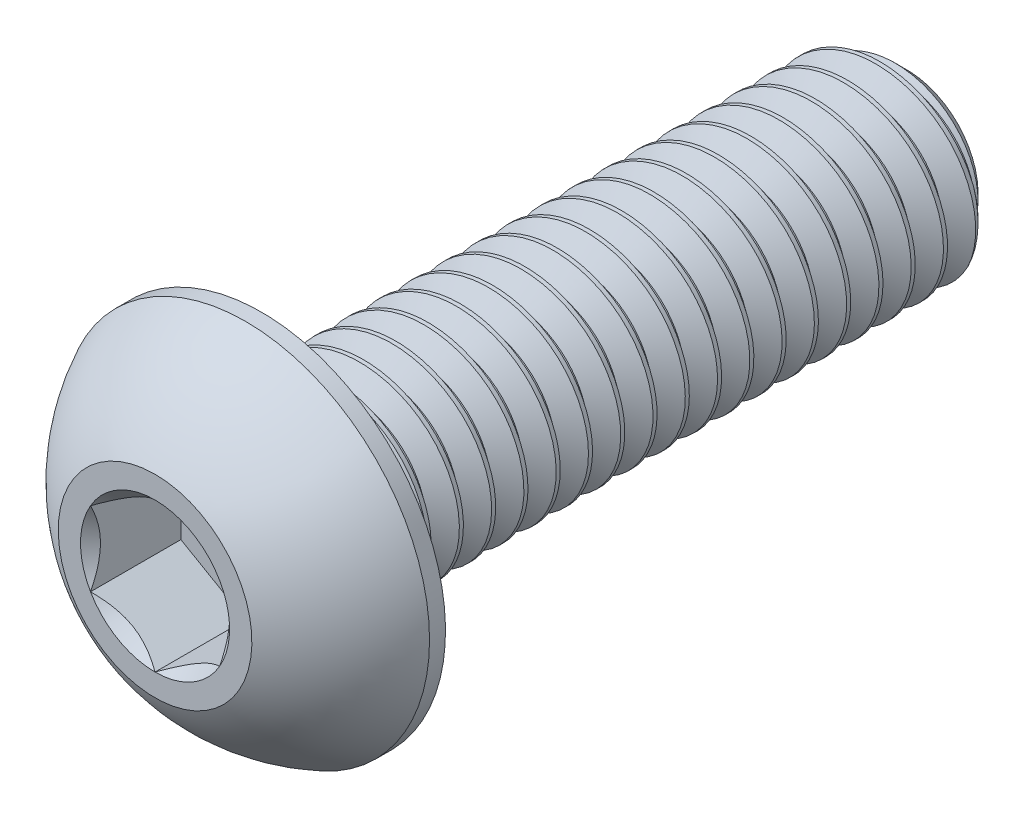
SolidWorks part; units mm, degrees
ref_plane "Front Plane" through (0, 0, 0) normal (0, 0, 1) x (1, 0, 0)
ref_plane "Top Plane" through (0, 0, 0) normal (0, 1, 0) x (1, 0, 0)
ref_plane "Right Plane" through (0, 0, 0) normal (1, 0, 0) x (0, 0, -1)
sketch "Sketch1" plane through (0, 0, 0) normal (1, 0, 0) x (0, 0, -1)
  line L0 (-5.825, 0) -> (5.825, 0) construction
  line L1 (-4.175, 2.85) -> (-4.175, -2.85) construction
  line L2 (5.825, 1.5) -> (5.825, -1.5) construction
  line L3 (5.7938, 1.5541) -> (6.0438, 1.1211) construction
  line L4 (6.0438, 1.1211) -> (6.2938, 1.5541) construction
  line L5 (6.2938, 1.5541) -> (5.7938, 1.5541) construction
  line L6 (5.825, 1.5) -> (6.2625, 1.5) construction
  line L7 (6.0438, 1.5541) -> (6.0438, 1.5) construction
  line L8 (6.0438, 1.5) -> (6.0438, 1.1752) construction
  line L9 (6.0438, 1.1752) -> (6.0438, 1.1211) construction
  line L10 (6.0125, 1.1752) -> (6.075, 1.1752)
  line L11 (5.8094, 1.5271) -> (6.2781, 1.5271)
  line L12 (6.075, 1.1752) -> (6.2781, 1.5271)
  line L13 (6.0125, 1.1752) -> (5.8094, 1.5271)
  line L14 (-5.825, 1) -> (-5.825, -1) construction
  line L15 (5.825, 1.5) -> (-4.175, 1.5) construction
  point P3 (-4.175, 0)
  point P6 (-4.425, 0)
  point P21 (6.0438, 1.5271)
  point P24 (-4.4225, 2.85)
  point P25 (4.575, -1.5)
  point P26 (-5.825, 1.5)
  dimension "Head Height" = 1.65
  dimension "Length" = 10
  dimension "Head Dia" = 5.7
  dimension "Thread Dia" = 3
  dimension "Pitch" = 0.5
  dimension "Drive Size" = 2
  dimension "D1" = 1.4
  dimension "D3" = 0.2475
  dimension "D4" = 1.25
sketch "Sketch2" plane through (0, 0, 0) normal (1, 0, 0) x (0, 0, -1)
  line L0 (-5.825, 0) -> (5.825, 0)
  line L1 (5.825, 0) -> (5.825, 1.1)
  line L2 (5.825, 1.5) -> (5.825, -1.5) construction
  line L3 (5.825, 1.1) -> (5.425, 1.5)
  line L4 (5.425, 1.5) -> (-4.175, 1.5)
  line L5 (-4.175, 2.85) -> (-4.175, -2.85) construction
  line L6 (-4.175, 1.5) -> (-4.175, 2.85)
  line L7 (-4.175, 2.85) -> (-4.4225, 2.85)
  line L8 (5.825, 1.5) -> (6.2625, 1.5) construction
  line L9 (-5.825, 0) -> (-5.825, 1.5)
  arc A0 (-5.825, 1.5) -> (-4.4225, 2.85) centre (-3.0302, 0) cw
  dimension "D1" = 0.4
  dimension "D2" = 45
revolve "Revolve1" add sketch "Sketch2" angle 360 about L0
sketch "Sketch3" plane through (0, 0, 5.825) normal (0, 0, 1) x (1, 0, 0)
  line L1 (0, 1.1547) -> (-1, 0.5774)
  line L2 (-1, 0.5774) -> (-1, -0.5774)
  line L3 (-1, -0.5774) -> (0, -1.1547)
  line L4 (0, -1.1547) -> (1, -0.5774)
  line L5 (1, -0.5774) -> (1, 0.5774)
  line L6 (1, 0.5774) -> (0, 1.1547)
  circle A0 centre (0, 0) radius 1 construction
  dimension "D1" = 2
extrude "Cut-Extrude1" cut sketch "Sketch3" against normal up to vertex (1.4 mm away) up to point (0, 0, 4.425)
sketch "Sketch4" plane through (0, 0, 5.825) normal (0, 0, 1) x (1, 0, 0)
  circle A0 centre (0, 0) radius 1.1547
extrude "Cut-Extrude2" cut sketch "Sketch4" against normal blind 10 draft 45
split "Split1" bodies to split 106 resulting bodies 107 108 split by face at (0, -2.85, 4.175)
sketch "Sketch5" plane through (0, 0, -5.825) normal (0, 0, -1) x (-1, 0, 0)
  circle A0 centre (0, 0) radius 1.5 construction
  circle A1 centre (0, 0) radius 1.5
curve "Helix/Spiral1" pitch 0.5 height 10.5 radius 1.5 centre (0, 0, -5.825) axis (0, 0, 1) start towards (0, 1, 0)
sketch "Sketch6" plane through (0, 0, 0) normal (1, 0, 0) x (0, 0, -1)
  line L0 (6.0125, 1.1752) -> (6.075, 1.1752) construction
  line L1 (6.0125, 1.1752) -> (5.8094, 1.5271) construction
  line L2 (5.8094, 1.5271) -> (6.2781, 1.5271) construction
  line L3 (6.075, 1.1752) -> (6.2781, 1.5271) construction
  line L4 (6.0125, 1.1752) -> (6.075, 1.1752)
  line L5 (6.0125, 1.1752) -> (5.8094, 1.5271)
  line L6 (5.8094, 1.5271) -> (6.2781, 1.5271)
  line L7 (6.075, 1.1752) -> (6.2781, 1.5271)
sweep "Cut-Sweep1" cut profiles "Sketch6" path "Helix/Spiral1" align with end faces yes
sketch "Sketch7" plane through (0, 0, 4.175) normal (0, 0, -1) x (-1, 0, 0)
  circle A1 centre (0, 0) radius 1.5
  circle A2 centre (0, 0) radius 1.5
  dimension "D1" = 0
extrude "Boss-Extrude1" add sketch "Sketch7" along normal blind 10 draft 30
equation "\"D2@Sketch1\" = \"Pitch@Sketch1\" / 8"
equation "\"D1@Sketch1\"=\"Drive Size@Sketch1\"*.7"
equation "\"D3@Sketch1\"=\"Head Height@Sketch1\"*.15"
equation "\"D1@Sketch2\"=\"Pitch@Sketch1\"*.8"
equation "\"D1@Sketch3\"=\"Drive Size@Sketch1\""
equation "\"D4@Helix/Spiral1\"=\"Pitch@Sketch1\""
equation "\"D3@Helix/Spiral1\"=\"Length@Sketch1\"+\"Pitch@Sketch1\""
equation "\"D4@Sketch1\"=\"Pitch@Sketch1\"*2.5"
